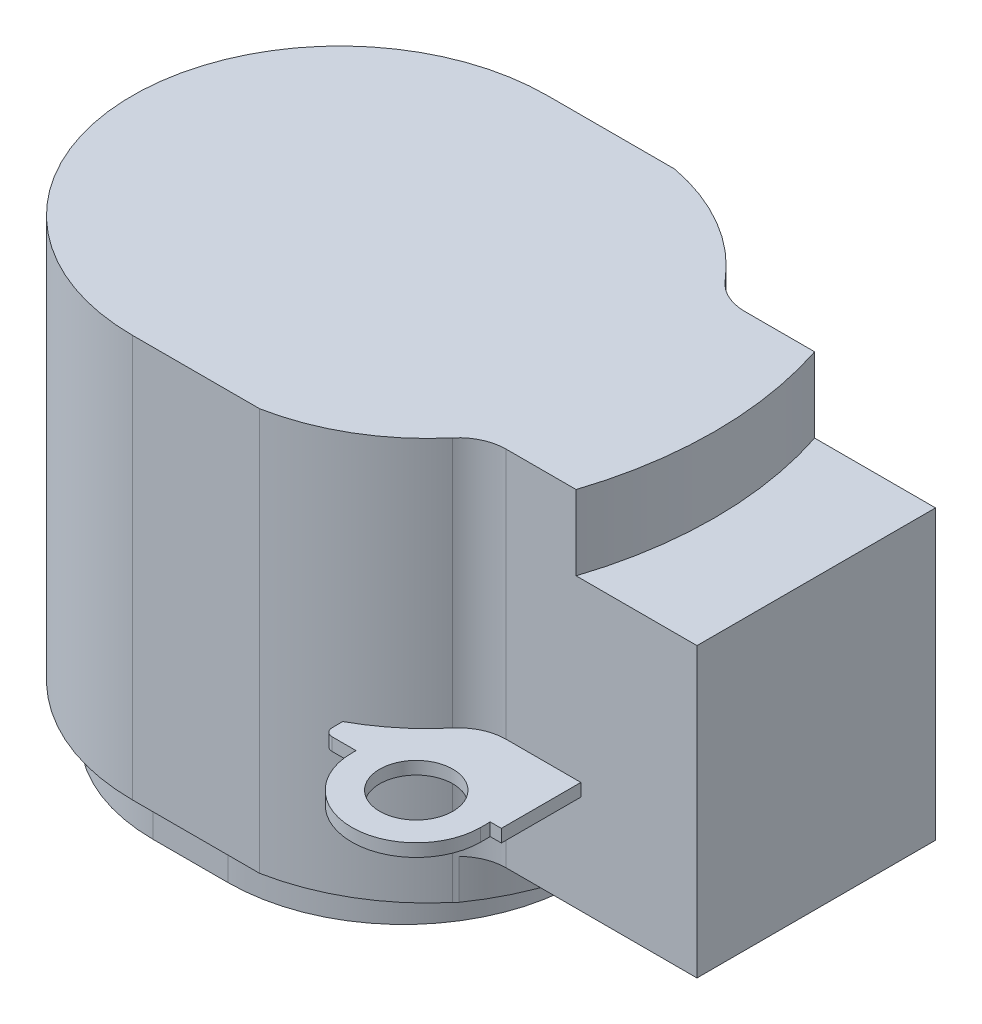
SolidWorks part; units mm, degrees
ref_plane "Front Plane" through (0, 0, 0) normal (0, 0, 1) x (1, 0, 0)
ref_plane "Top Plane" through (0, 0, 0) normal (0, 1, 0) x (1, 0, 0)
ref_plane "Right Plane" through (0, 0, 0) normal (1, 0, 0) x (0, 0, -1)
sketch "Sketch1" plane through (0, 0, 0) normal (0, 1, 0) x (1, 0, 0)
  line L5 (-4, 0) -> (1.4987, 0) construction
  line L6 (-4, 13.05) -> (4, 13.05)
  line L14 (-4, -13.05) -> (4, -13.05)
  line L16 (25.95, 7.5) -> (13.95, 7.5)
  line L17 (25.95, 7.5) -> (25.95, -7.5)
  line L18 (25.95, -7.5) -> (13.95, -7.5)
  arc A7 (-4, 13.05) -> (-4, -13.05) centre (-4, 0) ccw
  arc A8 (4, -13.05) -> (11.6566, -8.566) centre (1.4987, 0) ccw
  arc A9 (11.6566, 8.566) -> (4, 13.05) centre (1.4987, 0) ccw
  arc A10 (13.95, -7.5) -> (11.6566, -8.566) centre (13.95, -10.5) ccw
  arc A11 (13.95, 7.5) -> (11.6566, 8.566) centre (13.95, 10.5) cw
  point P2 (0, 0)
  point P11 (25.95, 0)
  point P17 (12.4673, 7.5)
  point P18 (-17.05, 0)
  dimension "D1" = 26.1
  dimension "D5" = 3
  dimension "D4" = 12
  dimension "D2" = 8
  dimension "D3" = 15
  dimension "D6" = 43
extrude "Boss-Extrude1" add sketch "Sketch1" against normal blind 28.8
sketch "Sketch2" plane through (0, 0, 0) normal (0, 1, 0) x (1, 0, 0)
  line L0 (0, 0) -> (-4.7, 0) construction
  line L1 (0, -9.05) -> (-4.7, -9.05)
  line L2 (0, 9.05) -> (-4.7, 9.05)
  arc A1 (0, -9.05) -> (0, 9.05) centre (0, 0) ccw
  arc A2 (-4.7, 9.05) -> (-4.7, -9.05) centre (-4.7, 0) ccw
  arc A4 (-4, 13.05) -> (-4, -13.05) centre (-4, 0) ccw construction
  point P3 (-2.35, 0)
  point P9 (-13.75, 0)
  point P17 (-17.05, 0)
  dimension "D1" = 3.3
  dimension "D2" = 18.1
extrude "Cut-Extrude1" cut sketch "Sketch2" against normal through all
sketch "Sketch7" plane through (0, 0, 0) normal (0, 1, 0) x (1, 0, 0)
  line L0 (-4.7, 0) -> (0, 0) construction
  line L1 (-4.7, 10.05) -> (0, 10.05)
  line L2 (-4.7, -10.05) -> (0, -10.05)
  line L3 (0, 9.05) -> (-4.7, 9.05) construction
  arc A0 (-4.7, 10.05) -> (-4.7, -10.05) centre (-4.7, 0) ccw
  arc A1 (0, -10.05) -> (0, 10.05) centre (0, 0) ccw
  point P4 (-2.35, 0)
  dimension "D1" = 1
extrude "Boss-Extrude3" add sketch "Sketch7" against normal blind 1
sketch "Sketch3" plane through (0, 0, 0) normal (0, 1, 0) x (1, 0, 0)
  line L1 (25.95, 7.5) -> (18.35, 7.5)
  line L2 (25.95, 7.5) -> (25.95, -7.5)
  line L3 (25.95, -7.5) -> (18.35, -7.5)
  line L6 (25.95, -7.5) -> (25.95, 7.5) construction
  arc A0 (18.35, 7.5) -> (18.35, -7.5) centre (-4.4875, 0) cw
  point P8 (19.55, 0)
  dimension "D2" = 1.2
  dimension "D1" = 7.6
extrude "Cut-Extrude2" cut sketch "Sketch3" against normal blind 4.7
ref_plane "Plane1" through (0, -15.8, 0) normal (0, 1, 0) x (1, 0, 0)
sketch "Sketch4" plane through (0, -15.8, 0) normal (0, 1, 0) x (1, 0, 0)
  line L0 (13.9, 13.1) -> (13.9, -13.1) construction
  line L1 (17.95, 13.1) -> (17.95, -13.1)
  line L2 (9.85, 13.1) -> (9.85, -13.1)
  line L4 (13.9, 0) -> (-21.7278, 0) construction
  line L5 (9.85, 12.8351) -> (8.35, 12.8351)
  line L6 (9.85, 12.8351) -> (9.85, 10.1067)
  line L7 (9.85, 10.1067) -> (7.85, 10.1067)
  line L8 (7.85, 12.3351) -> (7.85, 10.1067)
  line L10 (17.95, 12.5) -> (18.65, 12.5)
  line L11 (17.95, 12.5) -> (17.95, 6.669)
  line L12 (17.95, 6.669) -> (18.65, 6.669)
  line L13 (18.65, 12.5) -> (18.65, 6.669)
  line L22 (18.65, -12.5) -> (18.65, -6.669)
  line L23 (17.95, -6.669) -> (18.65, -6.669)
  line L24 (17.95, -12.5) -> (17.95, -6.669)
  line L25 (17.95, -12.5) -> (18.65, -12.5)
  line L26 (7.85, -12.3351) -> (7.85, -10.1067)
  line L27 (9.85, -10.1067) -> (7.85, -10.1067)
  line L28 (9.85, -12.8351) -> (9.85, -10.1067)
  line L29 (9.85, -12.8351) -> (8.35, -12.8351)
  line L30 (25.95, -7.5) -> (25.95, 7.5) construction
  line L31 (25.95, 7.5) -> (18.35, 7.5) construction
  arc A0 (17.95, 13.1) -> (9.85, 13.1) centre (13.9, 13.1) ccw
  arc A1 (9.85, -13.1) -> (17.95, -13.1) centre (13.9, -13.1) ccw
  circle A2 centre (13.9, 13.1) radius 2.3
  circle A3 centre (13.9, -13.1) radius 2.3
  arc A5 (8.35, 12.8351) -> (7.85, 12.3351) centre (8.35, 12.3351) ccw
  arc A6 (8.35, -12.8351) -> (7.85, -12.3351) centre (8.35, -12.3351) cw
  arc A8 (11.6566, 8.566) -> (4, 13.05) centre (1.4987, 0) ccw construction
  point P2 (13.9, 0)
  point P9 (13.9, 17.15)
  point P10 (13.9, -17.15)
  point P23 (9.85, 10.3351)
  point P43 (7.85, 12.8351)
  point P45 (7.85, -12.8351)
  point P46 (9.85, -10.3351)
  dimension "D2" = 4.05
  dimension "D4" = 4.6
  dimension "D5" = 4.6
  dimension "D6" = 2.5
  dimension "D10" = 0.5
  dimension "D3" = 34.3
  dimension "D7" = 2
  dimension "D8" = 8
  dimension "D9" = 0.7
  dimension "D11" = 5
extrude "Boss-Extrude2" add sketch "Sketch4" against normal blind 0.8 contours L26 A1 L1 A0 L6 L2 A3 A2 | L5 L8 L7 L2 L6 | L13 L10 L1 L12 | L1 L25 L22 L23 | L26 L2 A6 region at (13.9, -15.8, 0) region at (18.3, -15.8, -9.5845) region at (8.8588, -15.8, -11.4585) region at (18.3, -15.8, 9.5845) region at (8.8588, -15.8, 11.4585)
sketch "Sketch5" plane through (0, -28.8, 0) normal (0, -1, 0) x (1, 0, 0)
  line L0 (-4.7, 0) -> (0, 0) construction
  line L1 (-4.7, 11.05) -> (0, 11.05)
  line L2 (-4.7, -11.05) -> (0, -11.05)
  line L3 (-4.7, 9.05) -> (0, 9.05) construction
  arc A0 (-4.7, 11.05) -> (-4.7, -11.05) centre (-4.7, 0) ccw
  arc A1 (0, -11.05) -> (0, 11.05) centre (0, 0) ccw
  point P4 (-2.35, 0)
  arc M5 (0, 9.05) -> (0, -9.05) centre (0, 0) cw
  line M6 (0, -9.05) -> (-4.7, -9.05)
  arc M7 (-4.7, -9.05) -> (-4.7, 9.05) centre (-4.7, 0) cw
  line M8 (-4.7, 9.05) -> (0, 9.05)
  dimension "D1" = 2
extrude "Cut-Extrude3" cut sketch "Sketch5" against normal blind 3.5 flip side to cut contours L2 A1 L1 A0 M8 M5 M6 M7 region at (-2.35, -28.8, 10.7026)
sketch "Sketch6" plane through (0, -25.3, 0) normal (0, -1, 0) x (1, 0, 0)
  line L0 (7.85, 12.3351) -> (7.85, 11.6713) construction
  line L2 (-0.9152, 14.4718) -> (-20.7495, 14.4718)
  line L4 (0, -14.5007) -> (-20.7495, -14.5007)
  line L5 (-20.7495, 14.4718) -> (-20.7495, -14.5007)
  arc A0 (0, -14.5007) -> (-0.9152, 14.4718) centre (0, 0) ccw
  arc A2 (11.6566, 8.566) -> (13.95, 7.5) centre (13.95, 10.5) ccw construction
  point P3 (11.85, 8.3576)
  dimension "D1" = 4
extrude "Cut-Extrude4" cut sketch "Sketch6" against normal blind 2.5 flip side to cut
sketch "Sketch8" plane through (25.95, 0, 0) normal (1, 0, 0) x (0, 0, -1)
  line L0 (-11.05, -28.8) -> (11.05, -28.8) construction
  line L1 (-3.42, -15.98) -> (3.42, -15.98)
  line L2 (-3.42, -15.98) -> (-3.42, -21.98)
  line L3 (-3.42, -21.98) -> (3.42, -21.98)
  line L4 (3.42, -15.98) -> (3.42, -21.98)
  line L5 (-3.42, -15.98) -> (3.42, -21.98) construction
  line L6 (-3.42, -21.98) -> (3.42, -15.98) construction
  line L7 (-3.42, -5.03) -> (3.42, -5.03)
  line L8 (-3.42, -5.03) -> (-3.42, -11.03)
  line L9 (-3.42, -11.03) -> (3.42, -11.03)
  line L10 (3.42, -5.03) -> (3.42, -11.03)
  line L11 (-3.42, -5.03) -> (3.42, -11.03) construction
  line L12 (-3.42, -11.03) -> (3.42, -5.03) construction
  point P0 (0, -18.98)
  point P5 (0, -8.03)
  dimension "D1" = 6.84
  dimension "D2" = 6.84
  dimension "D3" = 6.82
  dimension "D4" = 17.77
  dimension "D5" = 6
  dimension "D6" = 6
extrude "Boss-Extrude4" add sketch "Sketch8" against normal blind 25
